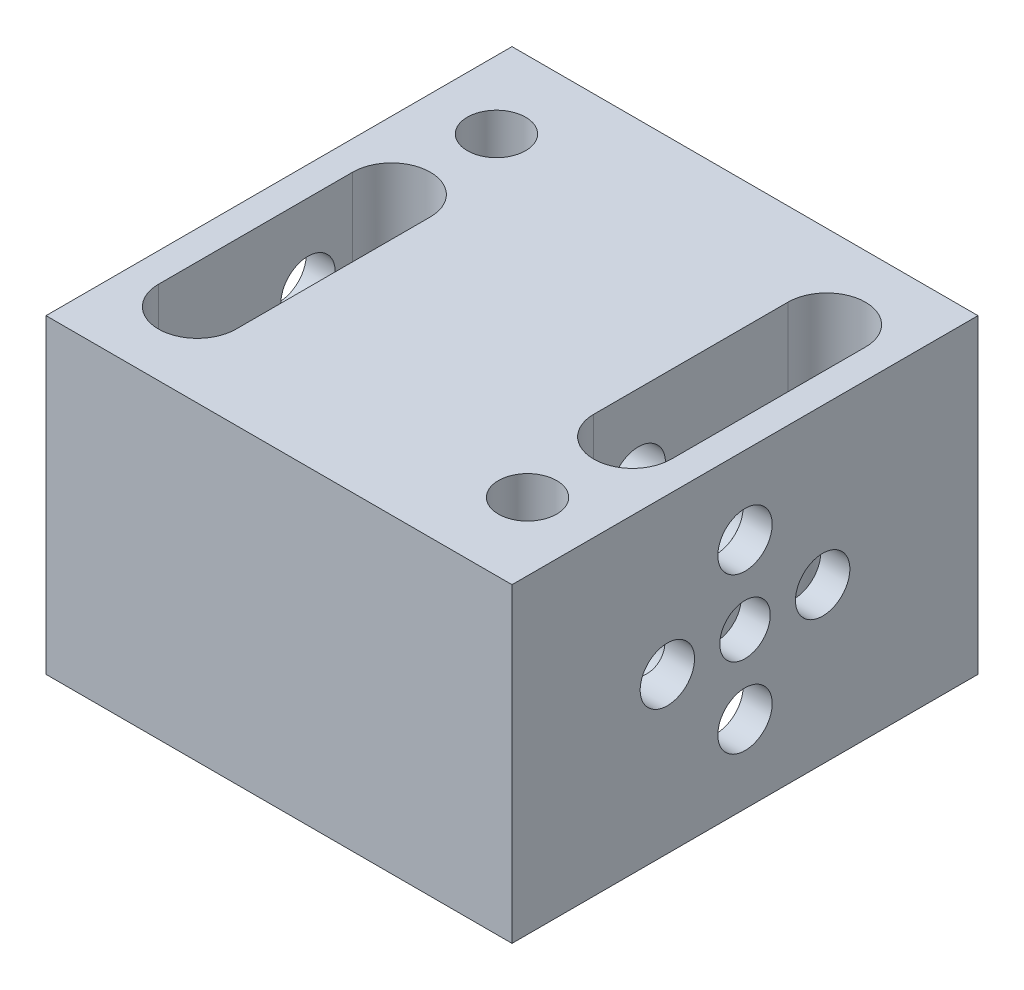
SolidWorks part; units mm, degrees
ref_plane "前视基准面" through (0, 0, 0) normal (0, 0, 1) x (1, 0, 0)
ref_plane "上视基准面" through (0, 0, 0) normal (0, 1, 0) x (1, 0, 0)
ref_plane "右视基准面" through (0, 0, 0) normal (1, 0, 0) x (0, 0, -1)
sketch "草图1" plane through (0, 0, 0) normal (1, 0, 0) x (0, 0, -1)
  line L1 (0, 0) -> (76.2, 0)
  line L2 (0, 0) -> (0, 50.8)
  line L3 (0, 50.8) -> (76.2, 50.8)
  line L4 (76.2, 0) -> (76.2, 50.8)
  circle A0 centre (38.1, 25.4) radius 4.1275
  circle A1 centre (25.4, 25.4) radius 4.445
  circle A2 centre (50.8, 25.4) radius 4.445
  circle A3 centre (38.1, 38.1) radius 4.445
  circle A4 centre (38.1, 12.7) radius 4.445
  dimension "D2" = 12.7
  dimension "D9" = 8.255
  dimension "D10" = 8.89
  dimension "D11" = 8.89
  dimension "D12" = 8.89
  dimension "D13" = 8.89
  dimension "D1" = 76.2
  dimension "D3" = 12.7
  dimension "D4" = 12.7
  dimension "D5" = 12.7
  dimension "D6" = 25.4
  dimension "D7" = 50.8
  dimension "D8" = 38.1
sketch "草图2" plane through (0, 0, 0) normal (1, 0, 0) x (0, 0, -1)
extrude "凸台-拉伸1" add sketch "草图1" along normal blind 76.2
sketch "草图3" plane through (0, 0, 0) normal (0, 1, 0) x (1, 0, 0)
  line L0 (11.0998, 45.3898) -> (11.0998, 13.6398) construction
  line L1 (0, 0) -> (76.2, 0)
  line L2 (0, 0) -> (0, 76.2)
  line L3 (0, 76.2) -> (76.2, 76.2)
  line L4 (76.2, 0) -> (76.2, 76.2)
  line L5 (17.4498, 45.3898) -> (17.4498, 13.6398)
  line L6 (4.7498, 45.3898) -> (4.7498, 13.6398)
  line L7 (65.1002, 30.8102) -> (65.1002, 62.5602) construction
  line L8 (58.7502, 30.8102) -> (58.7502, 62.5602)
  line L9 (71.4502, 30.8102) -> (71.4502, 62.5602)
  circle A0 centre (11.0998, 62.5602) radius 4.7625
  circle A1 centre (65.1002, 13.6398) radius 4.7625
  arc A2 (17.4498, 45.3898) -> (4.7498, 45.3898) centre (11.0998, 45.3898) ccw
  arc A3 (4.7498, 13.6398) -> (17.4498, 13.6398) centre (11.0998, 13.6398) ccw
  arc A4 (58.7502, 30.8102) -> (71.4502, 30.8102) centre (65.1002, 30.8102) ccw
  arc A5 (71.4502, 62.5602) -> (58.7502, 62.5602) centre (65.1002, 62.5602) ccw
  point P11 (11.0998, 29.5148)
  point P16 (65.1002, 46.6852)
  dimension "D5" = 9.525
  dimension "D8" = 9.525
  dimension "D9" = 6.35
  dimension "D10" = 31.75
  dimension "D11" = 6.35
  dimension "D1" = 76.2
  dimension "D2" = 76.2
  dimension "D3" = 11.0998
  dimension "D4" = 13.6398
  dimension "D6" = 13.6398
  dimension "D7" = 11.0998
  dimension "D12" = 31.75
extrude "凸台-拉伸2" add sketch "草图3" along normal blind 50.8
extrude "切除-拉伸2" cut sketch "草图1<4>" along normal blind 76.2 contours A3 | A1 | A4 | A0 | A2
sketch "草图1<4>" plane through (0, 0, 0) normal (1, 0, 0) x (0, 0, -1) same geometry as "草图1"
sketch "草图9" plane through (0, 0, 0) normal (0, 1, 0) x (1, 0, 0)
  line L4 (0, 76.2) -> (0, 0)
  line L5 (0, 0) -> (76.2, 0)
  line L6 (76.2, 0) -> (76.2, 76.2)
  line L7 (76.2, 76.2) -> (0, 76.2)
  line L8 (0, 76.2) -> (0, 0)
  line L9 (0, 0) -> (76.2, 0)
  line L10 (76.2, 0) -> (76.2, 76.2)
  line L11 (76.2, 76.2) -> (0, 76.2)
  dimension "D1" = 0
sketch "草图10" plane through (0, 0, 0) normal (0, 1, 0) x (1, 0, 0)
  line L0 (11.0998, 13.6398) -> (11.0998, 45.3898) construction
  line L1 (4.7498, 13.6398) -> (4.7498, 45.3898)
  line L2 (17.4498, 13.6398) -> (17.4498, 45.3898)
  line L3 (65.1002, 62.5602) -> (65.1002, 30.8102) construction
  line L4 (71.4502, 62.5602) -> (71.4502, 30.8102)
  line L5 (58.7502, 62.5602) -> (58.7502, 30.8102)
  circle A0 centre (11.0998, 62.5602) radius 4.7625
  circle A1 centre (65.1002, 13.6398) radius 4.7625
  arc A2 (4.7498, 13.6398) -> (17.4498, 13.6398) centre (11.0998, 13.6398) ccw
  arc A3 (17.4498, 45.3898) -> (4.7498, 45.3898) centre (11.0998, 45.3898) ccw
  arc A4 (71.4502, 62.5602) -> (58.7502, 62.5602) centre (65.1002, 62.5602) ccw
  arc A5 (58.7502, 30.8102) -> (71.4502, 30.8102) centre (65.1002, 30.8102) ccw
  point P6 (11.0998, 29.5148)
  point P11 (65.1002, 46.6852)
  dimension "D5" = 6.35
  dimension "D6" = 6.35
  dimension "D8" = 9.525
  dimension "D10" = 9.525
  dimension "D1" = 11.0998
  dimension "D2" = 11.0998
  dimension "D3" = 31.75
  dimension "D4" = 31.75
  dimension "D7" = 13.6398
  dimension "D9" = 13.6398
extrude "切除-拉伸3" cut sketch "草图10" along normal blind 50.8
